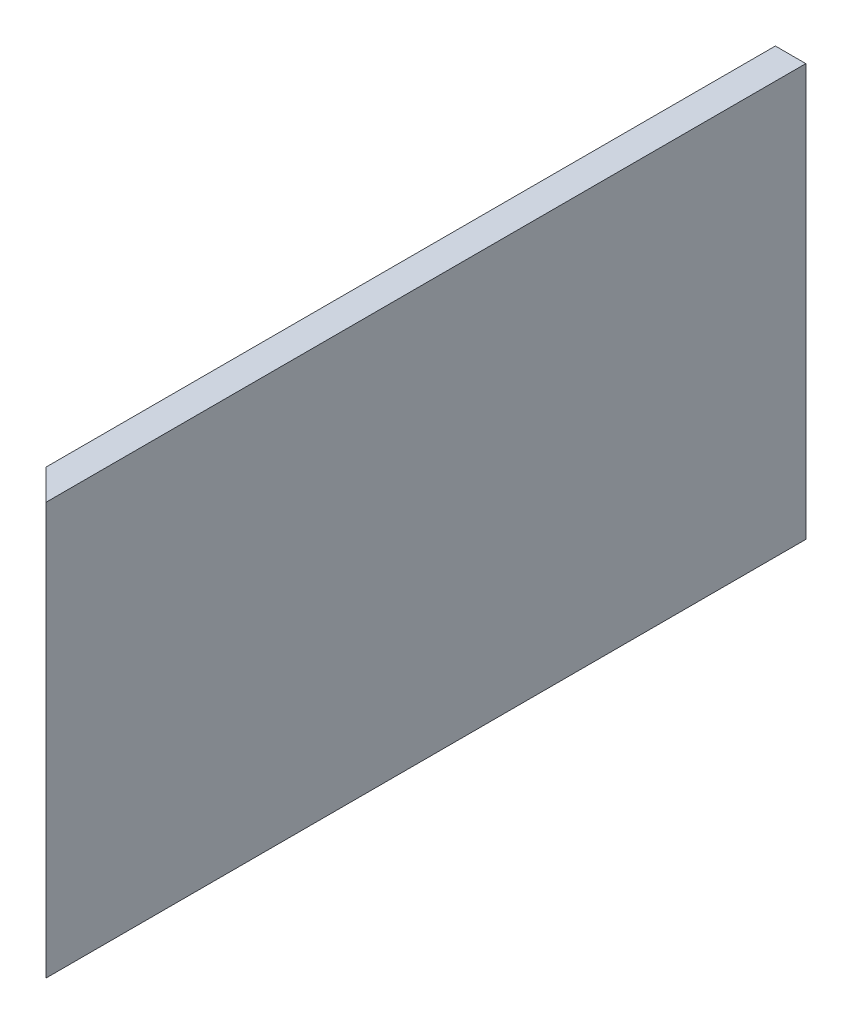
SolidWorks part; units mm, degrees
material "Cedar"
ref_plane "Front Plane" through (0, 0, 0) normal (0, 0, 1) x (1, 0, 0)
ref_plane "Top Plane" through (0, 0, 0) normal (0, 1, 0) x (1, 0, 0)
ref_plane "Right Plane" through (0, 0, 0) normal (1, 0, 0) x (0, 0, -1)
ref_plane "Plane1" through (0, 0, 0) normal (-0.7071, 0, 0.7071) x (0.7071, 0, 0.7071)
ref_plane "Plane2" through (0, 0, 0) normal (0.7071, 0, 0.7071) x (0.7071, 0, -0.7071)
sketch "Sketch2" plane through (0, 0, 0) normal (0, 0, 1) x (1, 0, 0)
  line L0 (303.8856, 0) -> (316.5856, 0)
  line L1 (316.5856, 0) -> (316.5856, 171.7294)
  line L2 (316.5856, 171.7294) -> (303.8856, 171.7294)
  line L3 (303.8856, 171.7294) -> (303.8856, 0)
  line L4 (0, 0) -> (303.8856, 0) construction
  line L5 (303.8856, 0) -> (303.8856, 177.6975) construction
  dimension "D1" = 0
  dimension "D2" = 12.7
  dimension "D3" = 171.7294
  dimension "D4" = 316.5856
  dimension "D5" = 171.7294
extrude "Boss-Extrude2" add sketch "Sketch2" along normal up to surface (316.5856 mm away) up to plane "Plane1"
mirror "Mirror1" [suppressed] about plane through (0, 0, 0) normal (-0.7071, 0, 0.7071)
